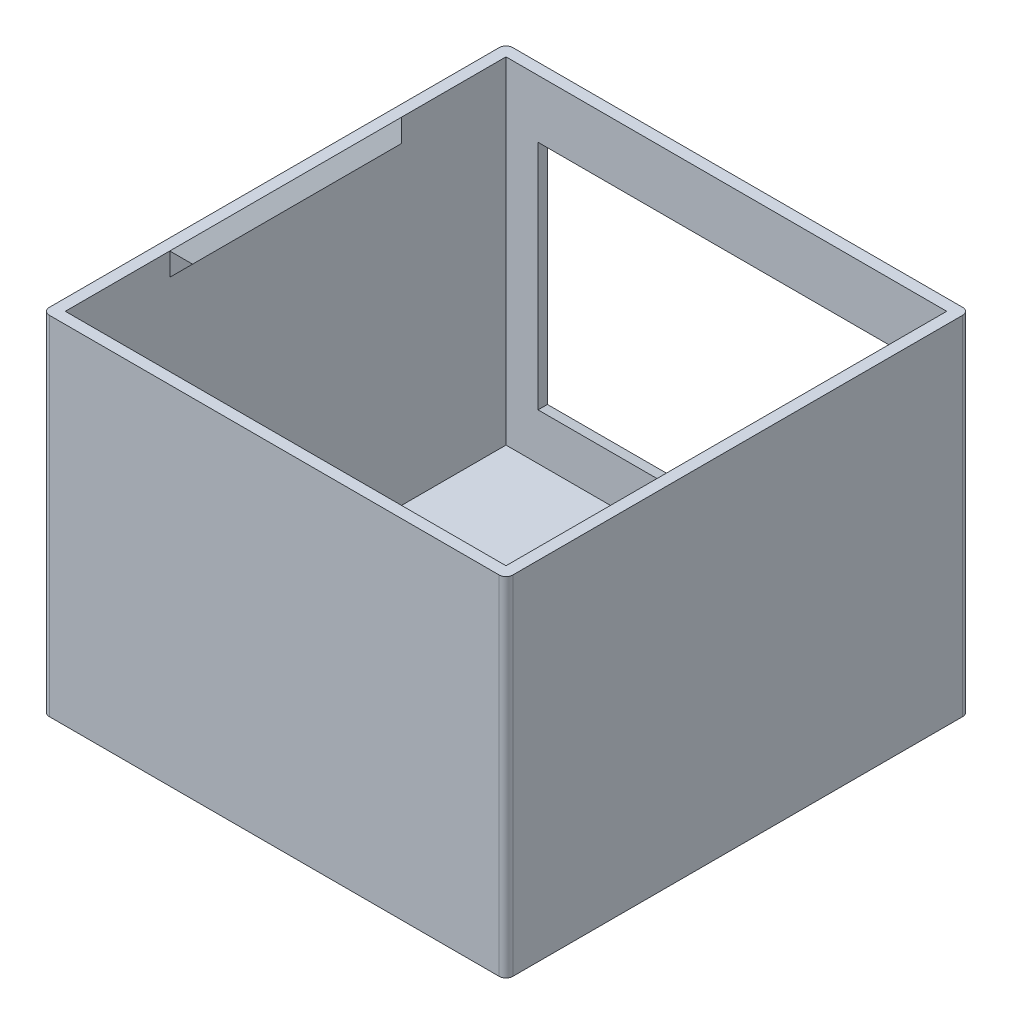
SolidWorks part; units mm, degrees
ref_plane "Front Plane" through (0, 0, 0) normal (0, 0, 1) x (1, 0, 0)
ref_plane "Top Plane" through (0, 0, 0) normal (0, 1, 0) x (1, 0, 0)
ref_plane "Right Plane" through (0, 0, 0) normal (1, 0, 0) x (0, 0, -1)
sketch "Sketch1" plane through (0, 0, 0) normal (0, 1, 0) x (1, 0, 0)
  line L1 (-3034.7935, 1995.1415) -> (-2831.5935, 1995.1415)
  line L2 (-3034.7935, 1995.1415) -> (-3034.7935, 1791.9415)
  line L3 (-3034.7935, 1791.9415) -> (-2831.5935, 1791.9415)
  line L4 (-2831.5935, 1995.1415) -> (-2831.5935, 1791.9415)
  line L5 (-2933.1935, 1791.9415) -> (-2933.1935, 1995.1415) construction
  line L6 (-3034.7935, 1893.5415) -> (-2831.5935, 1893.5415) construction
  point P144 (-2933.1935, 1893.5415)
  dimension "D1" = 203.2
  dimension "D2" = 203.2
extrude "Boss-Extrude1" add sketch "Sketch1" along normal blind 152.4
shell "Shell1" thickness 5 removed face at (-2933.1935, 152.4, -1893.5415)
fillet "Fillet1" radius 3 1 edges at (-3034.7935, 76.2, -1995.1415) type face fillet first side face at (-3034.7935, 76.2, -1893.5415) second side face at (-2933.1935, 76.2, -1995.1415)
fillet "Fillet2" radius 3 1 edges at (-3034.7935, 76.2, -1791.9415) type face fillet first side face at (-3034.7935, 76.2, -1892.0415) second side face at (-2933.1935, 76.2, -1791.9415)
fillet "Fillet3" radius 3 1 edges at (-2831.5935, 76.2, -1791.9415) type face fillet first side face at (-2931.6935, 76.2, -1791.9415) second side face at (-2831.5935, 76.2, -1893.5415)
fillet "Fillet4" radius 3 1 edges at (-2831.5935, 76.2, -1995.1415) type face fillet first side face at (-2831.5935, 76.2, -1895.0415) second side face at (-2931.6935, 76.2, -1995.1415)
sketch "Sketch2" plane through (-2836.5935, 0, 0) normal (-1, 0, 0) x (0, 0, 1)
  line L0 (-1796.9415, 152.4) -> (-1990.1415, 152.4) construction
  line L1 (-1944.3415, 152.4) -> (-1842.7415, 152.4)
  line L2 (-1944.3415, 152.4) -> (-1944.3415, 142.4)
  line L3 (-1944.3415, 142.4) -> (-1842.7415, 142.4)
  line L4 (-1842.7415, 152.4) -> (-1842.7415, 142.4)
  line L5 (-1893.5415, 142.4) -> (-1893.5415, 152.4) construction
  line L6 (-1944.3415, 147.4) -> (-1842.7415, 147.4) construction
  point P7 (-1893.5415, 152.4)
  point P204 (-1893.5415, 147.4)
  dimension "D1" = 10
  dimension "D2" = 101.6
extrude "Boss-Extrude2" add sketch "Sketch2" along normal blind 6 draft 45 contours L2 L1 L4 L3
ref_plane "Plane1" through (-2933.1935, 0, 0) normal (-1, 0, 0) x (0, 0, 1)
mirror "Mirror1" about plane through (-2933.1935, 0, 0) normal (-1, 0, 0) of "Boss-Extrude2"
sketch "Sketch7" plane through (0, 0, -1995.1415) normal (0, 0, -1) x (-1, 0, 0)
  line L0 (2933.1935, 127) -> (2933.1935, 152.4) construction
  line L1 (2850.6435, 127) -> (3015.7435, 127)
  line L2 (2850.6435, 127) -> (2850.6435, 25.4)
  line L3 (2850.6435, 25.4) -> (3015.7435, 25.4)
  line L4 (3015.7435, 127) -> (3015.7435, 25.4)
  line L5 (2933.1935, 25.4) -> (2933.1935, 127) construction
  line L6 (2850.6435, 76.2) -> (3015.7435, 76.2) construction
  line L7 (2834.5935, 152.4) -> (3031.7935, 152.4) construction
  line L8 (2933.1935, 25.4) -> (2933.1935, 0) construction
  line L9 (2834.5935, 0) -> (3031.7935, 0) construction
  line L10 (3015.7435, 76.2) -> (3031.7935, 76.2) construction
  line L11 (3031.7935, 0) -> (3031.7935, 152.4) construction
  line L12 (2850.6435, 76.2) -> (2834.5935, 76.2) construction
  line L13 (2834.5935, 152.4) -> (2834.5935, 0) construction
  point P340 (2933.1935, 76.2)
  dimension "D1" = 165.1
  dimension "D2" = 101.6
extrude "Cut-Extrude2" cut sketch "Sketch7" along normal blind 7 draft 10 from surface draft outward yes starting at face at (-2933.1935, 78.7, -1990.1415)
